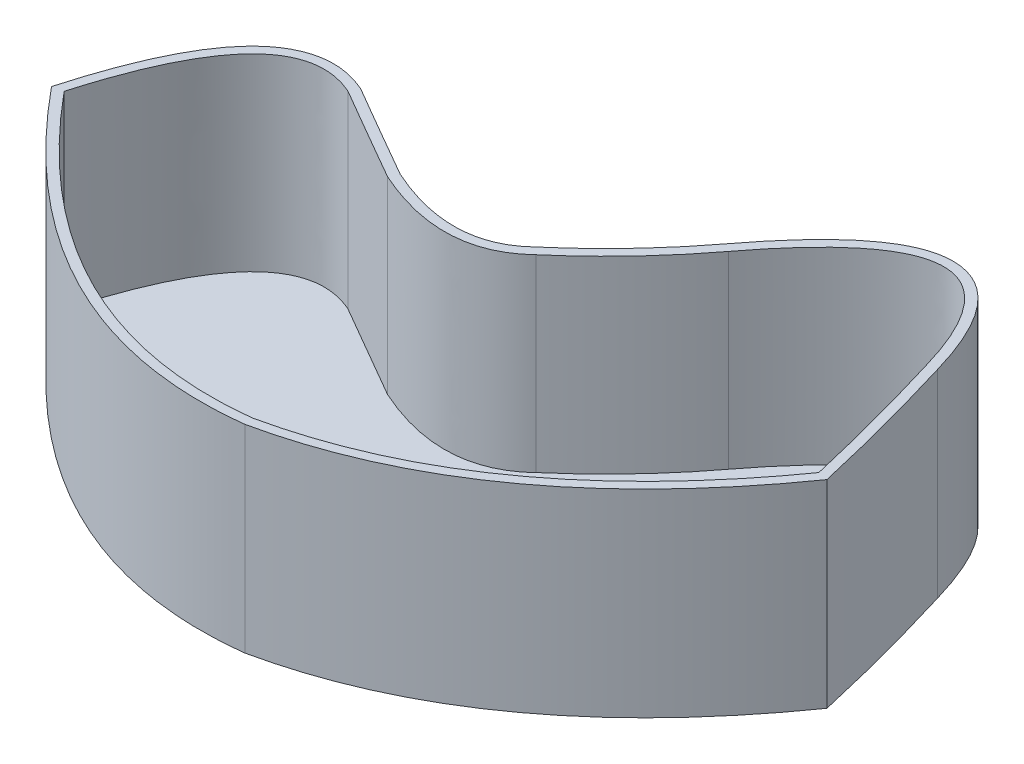
SolidWorks part; units mm, degrees
ref_plane "Alzado" through (0, 0, 0) normal (0, 0, 1) x (1, 0, 0)
ref_plane "Planta" through (0, 0, 0) normal (0, 1, 0) x (1, 0, 0)
ref_plane "Vista lateral" through (0, 0, 0) normal (1, 0, 0) x (0, 0, -1)
sketch "Croquis4" plane through (0, 0, 0) normal (0, 1, 0) x (1, 0, 0)
  spline S0 degree 2 poles (52.7103, 99.5821) (63.7566, 138.0816) (82.7103, 129.7359) knots 0 0 0 0.959481 0.959481 0.959481
  spline S1 degree 2 poles (82.7103, 129.7359) (92.672, 123.9233) (102.6588, 118.2012) knots 0 0 0 0.910186 0.910186 0.910186
  spline S2 degree 2 poles (102.6588, 118.2012) (122.1003, 109.4285) (132.7103, 119.5821) knots 0 0 0 0.908986 0.908986 0.908986
  spline S3 degree 3 poles (132.7103, 119.5821) (140.2326, 126.0368) (146.8991, 133.1053) (152.7239, 140.8711) knots 0 0 0 0 0.847217 0.847217 0.847217 0.847217
  spline S4 degree 2 poles (152.4499, 140.5072) (182.8083, 180.7849) (194.4542, 140.5072) knots 0 0 0 1 1 1
  spline S5 degree 2 poles (194.4542, 140.5072) (199.1361, 125.2041) (202.7103, 109.5821) knots 0 0 0 0.675598 0.675598 0.675598
  spline S7 degree 2 poles (202.7103, 109.5821) (173.4201, 68.3584) (132.7103, 59.5821) knots 0 0 0 0.720516 0.720516 0.720516
  spline S8 degree 2 poles (52.7103, 99.5821) (90.1265, 54.5188) (132.7103, 59.5821) knots 0 0 0 0.796719 0.796719 0.796719
  point P0 (52.7103, 99.5821)
  point P1 (82.7103, 129.7359)
  point P2 (132.7103, 119.5821)
  point P3 (182.7103, 159.5821)
  point P4 (202.7103, 109.5821)
  point P5 (132.7103, 59.5821)
  point P7 (102.6588, 118.2012)
  point P8 (152.4499, 140.5072)
  dimension "D1" = 150
  dimension "D2" = 40
  dimension "D3" = 70
  dimension "D4" = 50
  dimension "D5" = 100
  dimension "D6" = 30
  dimension "D7" = 20
  dimension "D8" = 50
  dimension "D9" = 60
extrude "Saliente-Extruir1" add sketch "Croquis4" along normal blind 2 contours S0 S8 S7 S5 S4 S3 S2 S1 region at (133.2531, 0, -103.325)
sketch "Croquis19" plane through (0, 2, 0) normal (0, 1, 0) x (1, 0, 0)
  arc A2 (83.6224, 131.5193) -> (103.5687, 119.9849) centre (1555.019, 2652.9786) ccw
  arc A3 (82.7103, 129.7359) -> (102.6588, 118.2012) centre (1555.019, 2652.9786) ccw
  arc A4 (82.7103, 129.7359) -> (102.6588, 118.2012) centre (1555.019, 2652.9786) ccw
  parabola Q18 (82.7103, 129.7359) -> (52.7103, 99.5821) focus (75.1294, 124.8336) apex (74.0808, 131.0457)
  parabola Q19 (52.7103, 99.5821) -> (132.7103, 59.5821) focus (120.56, 93.9941) apex (116.9977, 59.4379)
  parabola Q20 (132.7103, 59.5821) -> (202.7103, 109.5821) focus (128.3666, 109.8133) apex (144.8401, 63.0061)
  parabola Q21 (202.7103, 109.5821) -> (194.4542, 140.5072) focus (-16.9093, 71.9916) apex (196.5499, 133.4488)
  parabola Q22 (194.4542, 140.5072) -> (152.5485, 140.6379) focus (179.337, 155.4508) apex (180.482, 160.3801)
  parabola Q23 (132.7103, 119.5821) -> (102.6588, 118.2012) focus (123.5536, 124.3555) apex (127.47, 115.9624)
  parabola Q24 (82.7103, 129.7359) -> (52.7103, 99.5821) focus (75.1294, 124.8336) apex (74.0808, 131.0457)
  parabola Q25 (52.7103, 99.5821) -> (132.7103, 59.5821) focus (120.56, 93.9941) apex (116.9977, 59.4379)
  parabola Q26 (132.7103, 59.5821) -> (202.7103, 109.5821) focus (128.3666, 109.8133) apex (144.8401, 63.0061)
  parabola Q27 (202.7103, 109.5821) -> (194.4542, 140.5072) focus (-16.9093, 71.9916) apex (196.5499, 133.4488)
  parabola Q28 (194.4542, 140.5072) -> (152.5485, 140.6379) focus (179.337, 155.4508) apex (180.482, 160.3801)
  parabola Q29 (132.7103, 119.5821) -> (102.6588, 118.2012) focus (123.5536, 124.3555) apex (127.47, 115.9624)
  spline S2 degree 1 poles (83.6224, 131.5193) (50.5, 99.1178) knots 0 0 1 1 construction
  spline S3 degree 3 poles (-953.0233, 3981.382) (809.9139, -2406.0936) (929.9759, 1748.0259) (-3570.3993, -1273.9645) knots -23.003309 -23.003309 -23.003309 -23.003309 27.552014 27.552014 27.552014 27.552014 only from (152.5485, 140.6379) to (132.7103, 119.5821)
  spline S4 degree 3 poles (152.5485, 140.6379) (146.7654, 132.9638) (140.1572, 125.9721) (132.7103, 119.5821) knots 0 0 0 0 0.838729 0.838729 0.838729 0.838729
  spline S5 degree 1 poles (50.5, 99.1178) (133.04, 57.6073) knots 0 0 1 1 construction
  spline S6 degree 1 poles (133.04, 57.6073) (204.8585, 109.1563) knots 0 0 1 1 construction
  spline S7 degree 1 poles (204.8585, 109.1563) (196.3712, 141.0776) knots 0 0 1 1 construction
  spline S8 degree 1 poles (196.3712, 141.0776) (150.952, 141.8425) knots 0 0 1 1 construction
  spline S9 degree 1 poles (150.952, 141.8425) (131.3657, 121.0637) knots 0 0 1 1 construction
  spline S10 degree 1 poles (131.3657, 121.0637) (103.5687, 119.9849) knots 0 0 1 1 construction
  spline S11 degree 3 poles (83.6224, 131.5193) (83.1906, 131.712) (82.3062, 132.0748) (80.5656, 132.6583) (78.391, 133.1387) (75.809, 133.2904) (72.4282, 132.9107) (68.4092, 131.3379) (64.0744, 127.854) (60.1763, 122.9063) (57.2252, 117.5817) (55.0189, 112.5952) (53.4387, 108.492) (52.1795, 104.7611) (51.2105, 101.6055) (50.7306, 99.9418) (50.5, 99.1178) knots 0.499165 0.499165 0.499165 0.499165 0.499275 0.499384 0.499603 0.499822 0.50004 0.500478 0.500915 0.501353 0.50179 0.502009 0.502228 0.502446 0.502556 0.502665 0.502665 0.502665 0.502665
  spline S12 degree 3 poles (50.5, 99.1178) (51.2871, 98.1593) (52.8905, 96.2446) (56.0867, 92.5797) (60.1209, 88.2356) (65.0068, 83.4249) (71.5886, 77.5396) (79.9411, 71.1804) (90.1697, 65.1529) (100.6041, 60.7426) (111.2337, 57.9634) (120.2476, 57.0166) (127.5257, 57.0798) (131.2127, 57.3878) (133.04, 57.6073) knots 0.497081 0.497081 0.497081 0.497081 0.497193 0.497305 0.497529 0.497754 0.497978 0.498426 0.498874 0.499322 0.49977 0.500218 0.500442 0.500666 0.500666 0.500666 0.500666
  spline S13 degree 3 poles (133.04, 57.6073) (136.517, 58.3536) (143.4103, 60.2112) (153.3319, 64.0428) (162.8903, 68.9298) (172.064, 74.8642) (180.8547, 81.8417) (187.8594, 88.521) (193.2714, 94.3815) (197.2341, 99.0341) (200.4584, 103.1282) (202.9865, 106.527) (204.2414, 108.2788) (204.8585, 109.1563) knots 0.49955 0.49955 0.49955 0.49955 0.499921 0.500291 0.500661 0.501031 0.501401 0.501771 0.501957 0.502142 0.502327 0.502419 0.502512 0.502512 0.502512 0.502512
  spline S14 degree 3 poles (204.8585, 109.1563) (204.2494, 111.8432) (202.9812, 117.2076) (200.9329, 125.2083) (198.7377, 133.1676) (197.1762, 138.446) (196.3712, 141.0776) knots 0.499572 0.499572 0.499572 0.499572 0.49971 0.499848 0.499985 0.500123 0.500123 0.500123 0.500123
  spline S15 degree 3 poles (196.3712, 141.0776) (196.2488, 141.5006) (195.9954, 142.3523) (195.4807, 143.9861) (194.81, 145.9411) (193.9639, 148.1347) (192.7775, 150.8619) (191.1811, 153.9011) (188.359, 157.9749) (184.2382, 161.6038) (178.2217, 163.1507) (172.9281, 161.9163) (168.6153, 159.6543) (165.3038, 157.3362) (161.8979, 154.4065) (158.967, 151.4561) (156.5613, 148.7893) (154.7261, 146.6365) (153.1685, 144.7124) (151.9095, 143.1008) (151.2679, 142.2608) (150.952, 141.8425) knots 0.497989 0.497989 0.497989 0.497989 0.49806 0.49813 0.498272 0.498414 0.498556 0.49884 0.499123 0.499691 0.500258 0.500825 0.501109 0.501393 0.501676 0.50196 0.502102 0.502244 0.502386 0.502457 0.502527 0.502527 0.502527 0.502527
  spline S16 degree 3 poles (150.952, 141.8425) (149.5268, 139.9512) (146.5715, 136.2488) (141.8305, 130.9411) (136.7875, 125.8752) (133.1942, 122.6328) (131.3657, 121.0637) knots -0.000034 -0.000034 -0.000034 -0.000034 0.210053 0.420139 0.630226 0.840313 0.840313 0.840313 0.840313
  spline S17 degree 3 poles (131.3657, 121.0637) (130.9719, 120.6848) (130.1426, 119.9518) (128.4388, 118.6975) (126.1628, 117.4625) (123.1834, 116.5069) (119.9125, 116.0712) (116.3248, 116.1728) (113.0634, 116.7222) (110.2922, 117.4492) (108.1345, 118.1393) (106.2684, 118.8374) (104.7414, 119.4672) (103.9561, 119.8108) (103.5687, 119.9849) knots 0.49948 0.49948 0.49948 0.49948 0.499622 0.499765 0.500051 0.500336 0.500622 0.500907 0.501193 0.501336 0.501478 0.501621 0.501693 0.501764 0.501764 0.501764 0.501764
  dimension "D1" = 0
  dimension "D2" = 2
extrude "Saliente-Extruir2" add sketch "Croquis19" along normal blind 42 from offset 2 offset against normal yes
